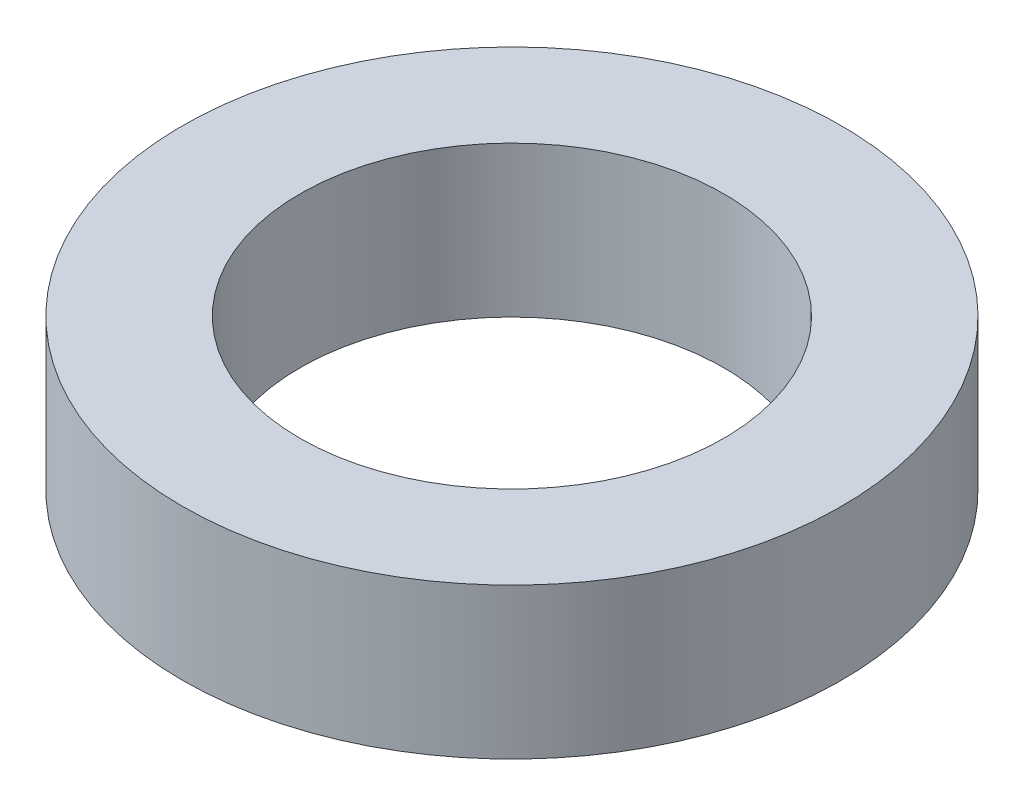
SolidWorks part; units mm, degrees
ref_plane "Front Plane" through (0, 0, 0) normal (0, 0, 1) x (1, 0, 0)
ref_plane "Top Plane" through (0, 0, 0) normal (0, 1, 0) x (1, 0, 0)
ref_plane "Right Plane" through (0, 0, 0) normal (1, 0, 0) x (0, 0, -1)
sketch "Sketch1" plane through (0, 0, 0) normal (0, 1, 0) x (1, 0, 0)
  circle A0 centre (0, 0) radius 35
  dimension "FLANGE_OD" = 70
extrude "Boss-Extrude1" add sketch "Sketch1" along normal blind 16
sketch "Sketch2" plane through (0, 0, 0) normal (0, 1, 0) x (1, 0, 0)
  circle A0 centre (0, 0) radius 22.5
  dimension "BORE_D" = 45
extrude "Cut-Extrude1" cut sketch "Sketch2" along normal through all
sketch "Sketch3" plane through (0, 16, 0) normal (0, 1, 0) x (1, 0, 0)
  circle A0 centre (0, 0) radius 15.138 construction
  circle A1 centre (-15.138, 0) radius 1.8491
  dimension "BOLT_D" = 3.6982
  dimension "BOLT_PCD" = 30.2761
extrude "Cut-Extrude2" cut sketch "Sketch3" against normal blind 14.5176 rebuild error yes
pattern_circular "CirPattern1" count 6 over 360 rebuild error yes
